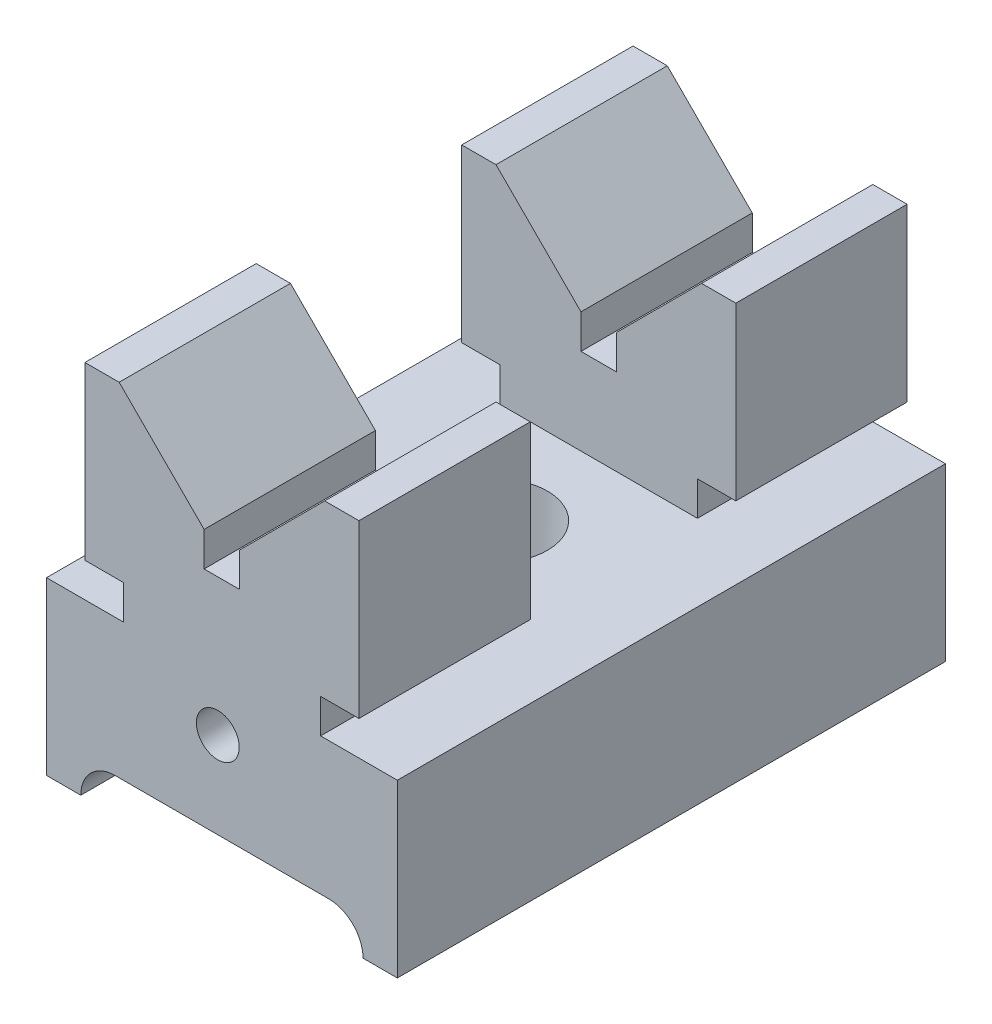
SolidWorks part; units mm, degrees
ref_plane "Front Plane" through (0, 0, 0) normal (0, 0, 1) x (1, 0, 0)
ref_plane "Top Plane" through (0, 0, 0) normal (0, 1, 0) x (1, 0, 0)
ref_plane "Right Plane" through (0, 0, 0) normal (1, 0, 0) x (0, 0, -1)
sketch "Sketch1" plane through (0, 0, 0) normal (0, 0, 1) x (1, 0, 0)
  line L0 (0, 0) -> (0, 31.75)
  line L1 (0, 31.75) -> (65.024, 31.75)
  line L2 (65.024, 31.75) -> (65.024, 0)
  line L3 (65.024, 0) -> (58.674, 0)
  line L4 (58.674, 0) -> (58.674, 6.35)
  line L5 (58.674, 6.35) -> (6.35, 6.35)
  line L6 (6.35, 6.35) -> (6.35, 0)
  line L7 (6.35, 0) -> (0, 0)
  dimension "D1" = 31.75
  dimension "D2" = 65.024
  dimension "D3" = 6.35
  dimension "D4" = 6.35
  dimension "D5" = 6.35
extrude "Boss-Extrude1" add sketch "Sketch1" against normal blind 101.6
fillet "Fillet1" radius 6.35 2 edges at (58.674, 6.35, -50.8) (6.35, 6.35, -50.8)
hole_wizard "3/8-16 Tapped Hole2" positions "Sketch4" profile "Sketch5" tap size "3/8-16" standard "ANSI Inch"
sketch "Sketch4" plane through (0, 0, 0) normal (0, 0, 1) x (1, 0, 0)
  line L0 (12.7, 6.35) -> (52.324, 6.35) construction
  line L2 (0, 31.75) -> (0, 0) construction
  point P0 (31.75, 22.352)
  dimension "D1" = 16.002
  dimension "D2" = 31.75
sketch "Sketch5" plane through (31.75, 22.352, 0) normal (1, 0, 0) x (0, -1, 0)
  line L0 (0, 0) -> (0, 18.3867)
  line L1 (0, 18.3867) -> (3.9687, 16.002)
  line L2 (3.9687, 16.002) -> (3.9687, 0)
  line L5 (3.9687, 0) -> (0, 0)
  line L10 (0, 18.3867) -> (-3.9688, 16.002) construction
  line L11 (0, -6.35) -> (0, 107.95) construction
  dimension "Tap Drill Dia." = 7.9375
  dimension "Tap Drill Depth" = 16.002
  dimension "Drill Angle" = 118
cosmetic thread "Hole Thread2" parameters "D1"=10.414, "D2"=9.525
sketch "Sketch7" plane through (0, 31.75, 0) normal (0, 1, 0) x (1, 0, 0)
  line L2 (65.024, 0) -> (0, 0) construction
  circle A0 centre (32.512, 50.8) radius 9.525
  point P3 (32.512, 0)
  dimension "D1" = 19.05
  dimension "D2" = 50.8
extrude "Cut-Extrude1" cut sketch "Sketch7" against normal through all
sketch "Sketch8" plane through (0, 0, 0) normal (0, 0, 1) x (1, 0, 0)
  line L0 (65.024, 31.75) -> (0, 31.75) construction
  line L1 (14.224, 31.75) -> (14.224, 38.1)
  line L2 (14.224, 38.1) -> (7.112, 38.1)
  line L3 (7.112, 38.1) -> (7.112, 69.85)
  line L4 (7.112, 69.85) -> (13.462, 69.85)
  line L5 (13.462, 69.85) -> (29.21, 54.102)
  line L6 (29.21, 54.102) -> (29.21, 47.752)
  line L7 (29.21, 47.752) -> (35.814, 47.752)
  line L8 (0, 0) -> (6.35, 0) construction
  line L9 (32.512, 31.75) -> (32.512, 71.3102) construction
  line L10 (50.8, 38.1) -> (57.912, 38.1)
  line L11 (35.814, 54.102) -> (35.814, 47.752)
  line L12 (51.562, 69.85) -> (35.814, 54.102)
  line L13 (57.912, 69.85) -> (51.562, 69.85)
  line L14 (57.912, 38.1) -> (57.912, 69.85)
  line L15 (50.8, 31.75) -> (50.8, 38.1)
  line L16 (0, 31.75) -> (0, 0) construction
  line L17 (14.224, 31.75) -> (50.8, 31.75)
  dimension "D1" = 38.1
  dimension "D2" = 69.85
  dimension "D3" = 50.8
  dimension "D4" = 44.45
  dimension "D5" = 28.702
  dimension "D6" = 47.752
  dimension "D7" = 50.8
  dimension "D8" = 90
extrude "Boss-Extrude2" add sketch "Sketch8" against normal blind 31.75
extrude "Boss-Extrude3" add sketch "Sketch8<3>" along normal blind 31.75 from surface starting at face at (32.512, 9.8538, -101.6)
sketch "Sketch8<3>" plane through (0, 0, 0) normal (0, 0, 1) x (1, 0, 0) same geometry as "Sketch8"
sketch "Sketch9" plane through (0, 0, 0) normal (-1, 0, 0) x (0, 0, 1)
  line L0 (-101.6, 31.75) -> (-101.6, 0) construction
  line L1 (-101.6, 0) -> (0, 0) construction
  circle A0 centre (-50.8, 16.002) radius 6.35
  dimension "D1" = 12.7
  dimension "D2" = 50.8
  dimension "D3" = 16.002
extrude "Cut-Extrude2" cut sketch "Sketch9" against normal blind 3.175
hole_wizard "3/8-16 Tapped Hole3" positions "Sketch10" profile "Sketch11" tap size "3/8-16" standard "ANSI Inch" end condition up to next
sketch "Sketch10" plane through (3.175, 0, 0) normal (-1, 0, 0) x (0, 0, 1)
  circle A0 centre (-50.8, 16.002) radius 6.35 construction
  point P0 (-50.8, 16.002)
  point P3 (0, 0)
sketch "Sketch11" plane through (3.175, 16.002, -50.8) normal (0, 1, 0) x (0, 0, 1)
  line L0 (0, 0) -> (0, 19.812)
  line L1 (0, 19.812) -> (3.9687, 19.812)
  line L2 (3.9687, 19.812) -> (3.9687, 0)
  line L5 (3.9687, 0) -> (0, 0)
  line L11 (0, -6.35) -> (0, 107.95) construction
  dimension "Thru Tap Drill Dia." = 7.9375
  dimension "Thru Tap Drill Depth" = 19.812
cosmetic thread "Hole Thread3" parameters "D2"=9.525
